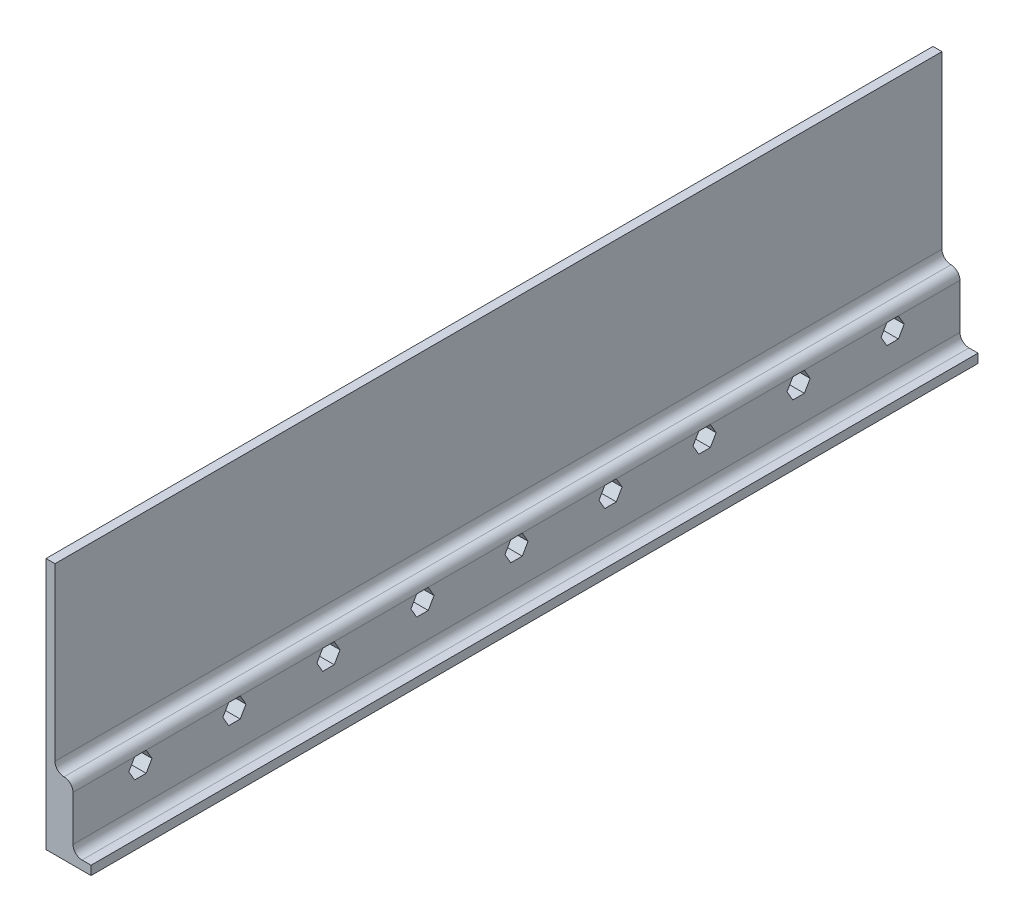
SolidWorks part; units mm, degrees
material "AISI 4340 Steel, annealed"
ref_plane "Front Plane" through (0, 0, 0) normal (0, 0, 1) x (1, 0, 0)
ref_plane "Top Plane" through (0, 0, 0) normal (0, 1, 0) x (1, 0, 0)
ref_plane "Right Plane" through (0, 0, 0) normal (1, 0, 0) x (0, 0, -1)
sketch "Sketch2" plane through (0, 0, 0) normal (0, 0, 1) x (1, 0, 0)
  line L0 (-12.5, 20) -> (12.5, -20) construction
  line L5 (-12.5, -20) -> (12.5, 20) construction
  line L6 (-12.5, 20) -> (-12.5, -20)
  line L7 (-12.5, -20) -> (12.5, -20)
  line L8 (12.5, -20) -> (12.5, -15)
  line L9 (12.5, -15) -> (2.5, -15)
  line L10 (2.5, -15) -> (2.5, 20)
  line L11 (2.5, 20) -> (-12.5, 20)
  point P4 (0, 0)
  point P6 (0, 0)
  dimension "D1" = 25
  dimension "D2" = 40
  dimension "D3" = 15
  dimension "D4" = 5
extrude "General extrude" add sketch "Sketch2" along normal mid plane 1850
fillet "Rounding" radius 5 2 edges at (2.5, 20, 0) (2.5, -15, 0)
sketch "Sketch3" plane through (-12.5, 0, 0) normal (-1, 0, 0) x (0, 0, 1)
  line L1 (-884.3763, 3.8875) -> (-881.1684, 9.4438)
  line L2 (-881.1684, 9.4438) -> (-884.3763, 15)
  line L3 (-884.3763, 15) -> (-890.7921, 15)
  line L4 (-890.7921, 15) -> (-894, 9.4438)
  line L5 (-894, 9.4438) -> (-890.7921, 3.8875)
  line L6 (-890.7921, 3.8875) -> (-884.3763, 3.8875)
  line L7 (-832.1655, 3.8875) -> (-828.9576, 9.4438)
  line L8 (-828.9576, 9.4438) -> (-832.1655, 15)
  line L9 (-832.1655, 15) -> (-838.5813, 15)
  line L10 (-838.5813, 15) -> (-841.7892, 9.4438)
  line L11 (-841.7892, 9.4438) -> (-838.5813, 3.8875)
  line L12 (-838.5813, 3.8875) -> (-832.1655, 3.8875)
  line L13 (-779.9546, 3.8875) -> (-776.7467, 9.4438)
  line L14 (-776.7467, 9.4438) -> (-779.9546, 15)
  line L15 (-779.9546, 15) -> (-786.3704, 15)
  line L16 (-786.3704, 15) -> (-789.5783, 9.4438)
  line L17 (-789.5783, 9.4438) -> (-786.3704, 3.8875)
  line L18 (-786.3704, 3.8875) -> (-779.9546, 3.8875)
  line L19 (-727.7438, 3.8875) -> (-724.5359, 9.4438)
  line L20 (-724.5359, 9.4438) -> (-727.7438, 15)
  line L21 (-727.7438, 15) -> (-734.1596, 15)
  line L22 (-734.1596, 15) -> (-737.3675, 9.4438)
  line L23 (-737.3675, 9.4438) -> (-734.1596, 3.8875)
  line L24 (-734.1596, 3.8875) -> (-727.7438, 3.8875)
  line L25 (-675.533, 3.8875) -> (-672.3251, 9.4438)
  line L26 (-672.3251, 9.4438) -> (-675.533, 15)
  line L27 (-675.533, 15) -> (-681.9488, 15)
  line L28 (-681.9488, 15) -> (-685.1567, 9.4438)
  line L29 (-685.1567, 9.4438) -> (-681.9488, 3.8875)
  line L30 (-681.9488, 3.8875) -> (-675.533, 3.8875)
  line L31 (-623.3221, 3.8875) -> (-620.1142, 9.4438)
  line L32 (-620.1142, 9.4438) -> (-623.3221, 15)
  line L33 (-623.3221, 15) -> (-629.7379, 15)
  line L34 (-629.7379, 15) -> (-632.9458, 9.4438)
  line L35 (-632.9458, 9.4438) -> (-629.7379, 3.8875)
  line L36 (-629.7379, 3.8875) -> (-623.3221, 3.8875)
  line L37 (-571.1113, 3.8875) -> (-567.9034, 9.4438)
  line L38 (-567.9034, 9.4438) -> (-571.1113, 15)
  line L39 (-571.1113, 15) -> (-577.5271, 15)
  line L40 (-577.5271, 15) -> (-580.735, 9.4438)
  line L41 (-580.735, 9.4438) -> (-577.5271, 3.8875)
  line L42 (-577.5271, 3.8875) -> (-571.1113, 3.8875)
  line L43 (-518.9004, 3.8875) -> (-515.6925, 9.4438)
  line L44 (-515.6925, 9.4438) -> (-518.9004, 15)
  line L45 (-518.9004, 15) -> (-525.3163, 15)
  line L46 (-525.3163, 15) -> (-528.5242, 9.4438)
  line L47 (-528.5242, 9.4438) -> (-525.3163, 3.8875)
  line L48 (-525.3163, 3.8875) -> (-518.9004, 3.8875)
  line L49 (-466.6896, 3.8875) -> (-463.4817, 9.4438)
  line L50 (-463.4817, 9.4438) -> (-466.6896, 15)
  line L51 (-466.6896, 15) -> (-473.1054, 15)
  line L52 (-473.1054, 15) -> (-476.3133, 9.4438)
  line L53 (-476.3133, 9.4438) -> (-473.1054, 3.8875)
  line L54 (-473.1054, 3.8875) -> (-466.6896, 3.8875)
  line L55 (-414.4788, 3.8875) -> (-411.2709, 9.4438)
  line L56 (-411.2709, 9.4438) -> (-414.4788, 15)
  line L57 (-414.4788, 15) -> (-420.8946, 15)
  line L58 (-420.8946, 15) -> (-424.1025, 9.4438)
  line L59 (-424.1025, 9.4438) -> (-420.8946, 3.8875)
  line L60 (-420.8946, 3.8875) -> (-414.4788, 3.8875)
  line L61 (-362.2679, 3.8875) -> (-359.06, 9.4438)
  line L62 (-359.06, 9.4438) -> (-362.2679, 15)
  line L63 (-362.2679, 15) -> (-368.6837, 15)
  line L64 (-368.6837, 15) -> (-371.8916, 9.4438)
  line L65 (-371.8916, 9.4438) -> (-368.6837, 3.8875)
  line L66 (-368.6837, 3.8875) -> (-362.2679, 3.8875)
  line L67 (-310.0571, 3.8875) -> (-306.8492, 9.4438)
  line L68 (-306.8492, 9.4438) -> (-310.0571, 15)
  line L69 (-310.0571, 15) -> (-316.4729, 15)
  line L70 (-316.4729, 15) -> (-319.6808, 9.4438)
  line L71 (-319.6808, 9.4438) -> (-316.4729, 3.8875)
  line L72 (-316.4729, 3.8875) -> (-310.0571, 3.8875)
  line L73 (-257.8463, 3.8875) -> (-254.6384, 9.4438)
  line L74 (-254.6384, 9.4438) -> (-257.8463, 15)
  line L75 (-257.8463, 15) -> (-264.2621, 15)
  line L76 (-264.2621, 15) -> (-267.47, 9.4438)
  line L77 (-267.47, 9.4438) -> (-264.2621, 3.8875)
  line L78 (-264.2621, 3.8875) -> (-257.8463, 3.8875)
  line L79 (-205.6354, 3.8875) -> (-202.4275, 9.4438)
  line L80 (-202.4275, 9.4438) -> (-205.6354, 15)
  line L81 (-205.6354, 15) -> (-212.0512, 15)
  line L82 (-212.0512, 15) -> (-215.2591, 9.4438)
  line L83 (-215.2591, 9.4438) -> (-212.0512, 3.8875)
  line L84 (-212.0512, 3.8875) -> (-205.6354, 3.8875)
  line L85 (-153.4246, 3.8875) -> (-150.2167, 9.4438)
  line L86 (-150.2167, 9.4438) -> (-153.4246, 15)
  line L87 (-153.4246, 15) -> (-159.8404, 15)
  line L88 (-159.8404, 15) -> (-163.0483, 9.4438)
  line L89 (-163.0483, 9.4438) -> (-159.8404, 3.8875)
  line L90 (-159.8404, 3.8875) -> (-153.4246, 3.8875)
  line L91 (-101.2138, 3.8875) -> (-98.0059, 9.4438)
  line L92 (-98.0059, 9.4438) -> (-101.2138, 15)
  line L93 (-101.2138, 15) -> (-107.6296, 15)
  line L94 (-107.6296, 15) -> (-110.8375, 9.4438)
  line L95 (-110.8375, 9.4438) -> (-107.6296, 3.8875)
  line L96 (-107.6296, 3.8875) -> (-101.2138, 3.8875)
  line L97 (-49.0029, 3.8875) -> (-45.795, 9.4438)
  line L98 (-45.795, 9.4438) -> (-49.0029, 15)
  line L99 (-49.0029, 15) -> (-55.4187, 15)
  line L100 (-55.4187, 15) -> (-58.6266, 9.4438)
  line L101 (-58.6266, 9.4438) -> (-55.4187, 3.8875)
  line L102 (-55.4187, 3.8875) -> (-49.0029, 3.8875)
  line L103 (3.2079, 3.8875) -> (6.4158, 9.4438)
  line L104 (6.4158, 9.4438) -> (3.2079, 15)
  line L105 (3.2079, 15) -> (-3.2079, 15)
  line L106 (-3.2079, 15) -> (-6.4158, 9.4438)
  line L107 (-6.4158, 9.4438) -> (-3.2079, 3.8875)
  line L108 (-3.2079, 3.8875) -> (3.2079, 3.8875)
  line L109 (55.4187, 3.8875) -> (58.6266, 9.4438)
  line L110 (58.6266, 9.4438) -> (55.4187, 15)
  line L111 (55.4187, 15) -> (49.0029, 15)
  line L112 (49.0029, 15) -> (45.795, 9.4438)
  line L113 (45.795, 9.4438) -> (49.0029, 3.8875)
  line L114 (49.0029, 3.8875) -> (55.4187, 3.8875)
  line L115 (107.6296, 3.8875) -> (110.8375, 9.4438)
  line L116 (110.8375, 9.4438) -> (107.6296, 15)
  line L117 (107.6296, 15) -> (101.2138, 15)
  line L118 (101.2138, 15) -> (98.0059, 9.4438)
  line L119 (98.0059, 9.4438) -> (101.2138, 3.8875)
  line L120 (101.2138, 3.8875) -> (107.6296, 3.8875)
  line L121 (159.8404, 3.8875) -> (163.0483, 9.4438)
  line L122 (163.0483, 9.4438) -> (159.8404, 15)
  line L123 (159.8404, 15) -> (153.4246, 15)
  line L124 (153.4246, 15) -> (150.2167, 9.4438)
  line L125 (150.2167, 9.4438) -> (153.4246, 3.8875)
  line L126 (153.4246, 3.8875) -> (159.8404, 3.8875)
  line L127 (212.0512, 3.8875) -> (215.2591, 9.4438)
  line L128 (215.2591, 9.4438) -> (212.0512, 15)
  line L129 (212.0512, 15) -> (205.6354, 15)
  line L130 (205.6354, 15) -> (202.4275, 9.4438)
  line L131 (202.4275, 9.4438) -> (205.6354, 3.8875)
  line L132 (205.6354, 3.8875) -> (212.0512, 3.8875)
  line L133 (264.2621, 3.8875) -> (267.47, 9.4438)
  line L134 (267.47, 9.4438) -> (264.2621, 15)
  line L135 (264.2621, 15) -> (257.8463, 15)
  line L136 (257.8463, 15) -> (254.6384, 9.4438)
  line L137 (254.6384, 9.4438) -> (257.8463, 3.8875)
  line L138 (257.8463, 3.8875) -> (264.2621, 3.8875)
  line L139 (316.4729, 3.8875) -> (319.6808, 9.4438)
  line L140 (319.6808, 9.4438) -> (316.4729, 15)
  line L141 (316.4729, 15) -> (310.0571, 15)
  line L142 (310.0571, 15) -> (306.8492, 9.4438)
  line L143 (306.8492, 9.4438) -> (310.0571, 3.8875)
  line L144 (310.0571, 3.8875) -> (316.4729, 3.8875)
  line L145 (368.6837, 3.8875) -> (371.8916, 9.4438)
  line L146 (371.8916, 9.4438) -> (368.6837, 15)
  line L147 (368.6837, 15) -> (362.2679, 15)
  line L148 (362.2679, 15) -> (359.06, 9.4438)
  line L149 (359.06, 9.4438) -> (362.2679, 3.8875)
  line L150 (362.2679, 3.8875) -> (368.6837, 3.8875)
  line L151 (420.8946, 3.8875) -> (424.1025, 9.4438)
  line L152 (424.1025, 9.4438) -> (420.8946, 15)
  line L153 (420.8946, 15) -> (414.4788, 15)
  line L154 (414.4788, 15) -> (411.2709, 9.4438)
  line L155 (411.2709, 9.4438) -> (414.4788, 3.8875)
  line L156 (414.4788, 3.8875) -> (420.8946, 3.8875)
  line L157 (473.1054, 3.8875) -> (476.3133, 9.4438)
  line L158 (476.3133, 9.4438) -> (473.1054, 15)
  line L159 (473.1054, 15) -> (466.6896, 15)
  line L160 (466.6896, 15) -> (463.4817, 9.4438)
  line L161 (463.4817, 9.4438) -> (466.6896, 3.8875)
  line L162 (466.6896, 3.8875) -> (473.1054, 3.8875)
  line L163 (525.3163, 3.8875) -> (528.5242, 9.4438)
  line L164 (528.5242, 9.4438) -> (525.3163, 15)
  line L165 (525.3163, 15) -> (518.9004, 15)
  line L166 (518.9004, 15) -> (515.6925, 9.4438)
  line L167 (515.6925, 9.4438) -> (518.9004, 3.8875)
  line L168 (518.9004, 3.8875) -> (525.3163, 3.8875)
  line L169 (577.5271, 3.8875) -> (580.735, 9.4438)
  line L170 (580.735, 9.4438) -> (577.5271, 15)
  line L171 (577.5271, 15) -> (571.1113, 15)
  line L172 (571.1113, 15) -> (567.9034, 9.4438)
  line L173 (567.9034, 9.4438) -> (571.1113, 3.8875)
  line L174 (571.1113, 3.8875) -> (577.5271, 3.8875)
  line L175 (629.7379, 3.8875) -> (632.9458, 9.4438)
  line L176 (632.9458, 9.4438) -> (629.7379, 15)
  line L177 (629.7379, 15) -> (623.3221, 15)
  line L178 (623.3221, 15) -> (620.1142, 9.4438)
  line L179 (620.1142, 9.4438) -> (623.3221, 3.8875)
  line L180 (623.3221, 3.8875) -> (629.7379, 3.8875)
  line L181 (681.9488, 3.8875) -> (685.1567, 9.4438)
  line L182 (685.1567, 9.4438) -> (681.9488, 15)
  line L183 (681.9488, 15) -> (675.533, 15)
  line L184 (675.533, 15) -> (672.3251, 9.4438)
  line L185 (672.3251, 9.4438) -> (675.533, 3.8875)
  line L186 (675.533, 3.8875) -> (681.9488, 3.8875)
  line L187 (734.1596, 3.8875) -> (737.3675, 9.4438)
  line L188 (737.3675, 9.4438) -> (734.1596, 15)
  line L189 (734.1596, 15) -> (727.7438, 15)
  line L190 (727.7438, 15) -> (724.5359, 9.4438)
  line L191 (724.5359, 9.4438) -> (727.7438, 3.8875)
  line L192 (727.7438, 3.8875) -> (734.1596, 3.8875)
  line L193 (786.3704, 3.8875) -> (789.5783, 9.4438)
  line L194 (789.5783, 9.4438) -> (786.3704, 15)
  line L195 (786.3704, 15) -> (779.9546, 15)
  line L196 (779.9546, 15) -> (776.7467, 9.4438)
  line L197 (776.7467, 9.4438) -> (779.9546, 3.8875)
  line L198 (779.9546, 3.8875) -> (786.3704, 3.8875)
  line L199 (838.5813, 3.8875) -> (841.7892, 9.4438)
  line L200 (841.7892, 9.4438) -> (838.5813, 15)
  line L201 (838.5813, 15) -> (832.1655, 15)
  line L202 (832.1655, 15) -> (828.9576, 9.4438)
  line L203 (828.9576, 9.4438) -> (832.1655, 3.8875)
  line L204 (832.1655, 3.8875) -> (838.5813, 3.8875)
  line L205 (890.7921, 3.8875) -> (894, 9.4438)
  line L206 (894, 9.4438) -> (890.7921, 15)
  line L207 (890.7921, 15) -> (884.3763, 15)
  line L208 (884.3763, 15) -> (881.1684, 9.4438)
  line L209 (881.1684, 9.4438) -> (884.3763, 3.8875)
  line L210 (884.3763, 3.8875) -> (890.7921, 3.8875)
  line L212 (925, 20) -> (925, -20) construction
  line L213 (-925, 20) -> (-925, -20) construction
  line L215 (925, 20) -> (-925, 20) construction
  circle A0 centre (-887.5842, 9.4438) radius 5.5563 construction
  circle A1 centre (-835.3734, 9.4438) radius 5.5563 construction
  point P222 (-835.3734, 15)
  dimension "D1" = 11.1125
  dimension "D2" = 5
  dimension "D4" = 31
  dimension "D5" = 31
  dimension "D3" = 35
extrude "Roller holders" cut sketch "Sketch3" against normal through all
sketch "Sketch5" plane through (0, 20, 0) normal (0, 1, 0) x (1, 0, 0)
  line L0 (-2.5, -925) -> (-12.5, -925) construction
  line L1 (-12.5, 925) -> (-7.5, 925)
  line L2 (-12.5, 925) -> (-12.5, -925)
  line L3 (-12.5, -925) -> (-7.5, -925)
  line L4 (-7.5, 925) -> (-7.5, -925)
  dimension "D1" = 5
extrude "Guard rail" add sketch "Sketch5" along normal blind 100
fillet "Guard rail support fillet" radius 5 1 edges at (-7.5, 20, 0)
sketch "Sketch6" plane through (-12.5, 0, 0) normal (-1, 0, 0) x (0, 0, 1)
  line L0 (925, -20) -> (-925, -20) construction
  line L1 (-925, 120) -> (432.48, 120)
  line L2 (-925, 120) -> (-925, -20)
  line L3 (-925, -20) -> (432.48, -20)
  line L4 (432.48, 120) -> (432.48, -20)
  line L5 (925, 120) -> (925, -20) construction
  dimension "D1" = 492.52
extrude "CUT TO SIZE" cut sketch "Sketch6" against normal through all both and the other way through all
